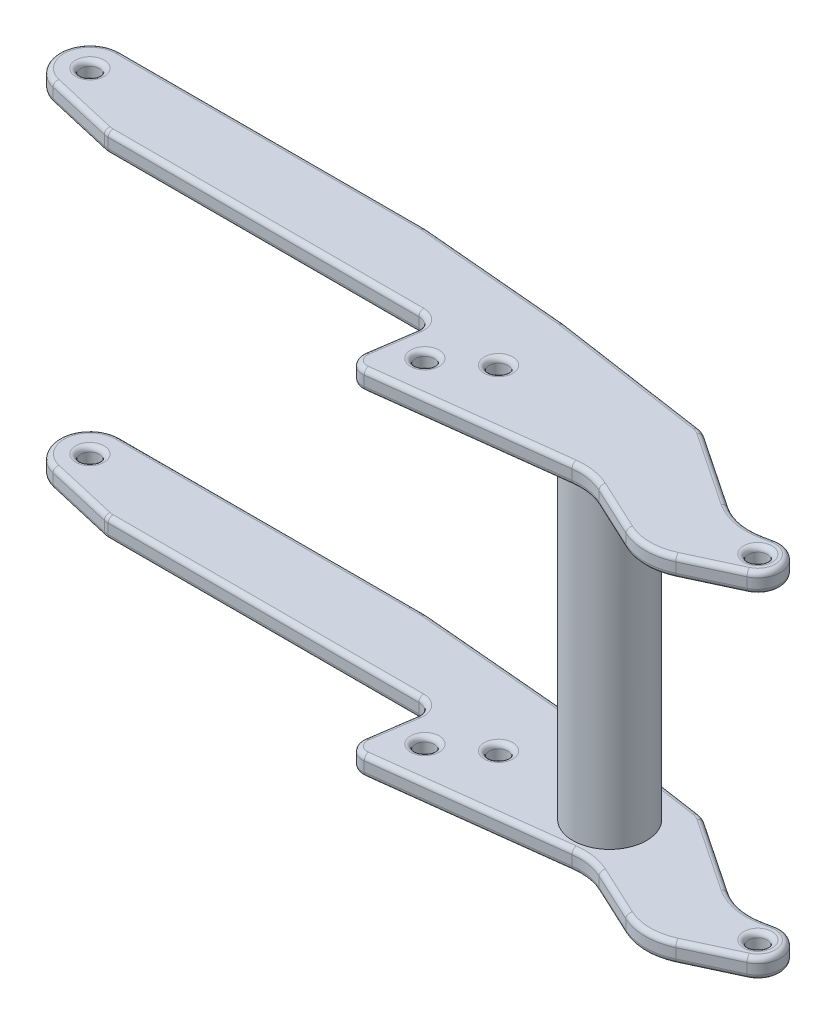
SolidWorks part; units mm, degrees
ref_plane "Front Plane" through (0, 0, 0) normal (0, 0, 1) x (1, 0, 0)
ref_plane "Top Plane" through (0, 0, 0) normal (0, 1, 0) x (1, 0, 0)
ref_plane "Right Plane" through (0, 0, 0) normal (1, 0, 0) x (0, 0, -1)
sketch "Sketch1" plane through (0, 0, 0) normal (0, 1, 0) x (1, 0, 0)
  line L0 (2.2619, 2.5389) -> (11.3096, 2.5389) construction
  line L1 (0, 3.125) -> (31.1, 3.125)
  line L2 (31.1, 3.125) -> (46.5, 1.7777)
  line L3 (46.5, 1.7777) -> (63, -0.6441)
  line L4 (63, -0.6441) -> (70.831, -5.8964)
  line L5 (75.3488, -6.7971) -> (76.2867, -6.6097)
  line L6 (76.806, -8.8246) -> (76.806, -2.115) construction
  line L7 (77.7673, -10.8865) -> (72.8208, -13.1928)
  line L8 (67.7494, -13.1926) -> (62.6097, -10.7957)
  line L9 (59.3428, -10.2781) -> (40.5062, -12.5902)
  line L10 (38.8949, -10.9405) -> (39.5728, -6.3216)
  line L11 (38.1382, -4.661) -> (6.297, -4.661)
  line L12 (6.297, -4.661) -> (-0.703, -3.0449)
  circle A0 centre (0, 0) radius 0.95
  arc A1 (0, 3.125) -> (-0.703, -3.0449) centre (0, 0) ccw
  arc A2 (70.831, -5.8964) -> (75.3488, -6.7971) centre (74.1731, -0.9134) ccw
  circle A3 centre (76.806, -8.8246) radius 0.95
  arc A4 (76.2867, -6.6097) -> (77.7673, -10.8865) centre (76.806, -8.8246) cw
  arc A5 (72.8208, -13.1928) -> (67.7494, -13.1926) centre (70.2853, -7.7549) cw
  arc A6 (62.6097, -10.7957) -> (59.3428, -10.2781) centre (60.0738, -16.2334) ccw
  arc A7 (40.5062, -12.5902) -> (38.8949, -10.9405) centre (40.3295, -11.151) cw
  arc A8 (39.5728, -6.3216) -> (38.1382, -4.661) centre (38.1382, -6.111) ccw
  circle A9 centre (42.6057, -8.5156) radius 0.95
  circle A10 centre (46.9557, -5.3656) radius 0.95
  point P18 (73, -6.7976)
  point P29 (38.6187, -12.8219)
  dimension "D1" = 1.9
  dimension "D2" = 3.125
  dimension "D9" = 6
  dimension "D10" = 0.5193
  dimension "D15" = 1.9
  dimension "D16" = 6
  dimension "D20" = 6
  dimension "D24" = 1.45
  dimension "D25" = 1.45
  dimension "D28" = 1.9
  dimension "D29" = 1.9
  dimension "D3" = 31.1
  dimension "D4" = 175
  dimension "D5" = 46.5
  dimension "D6" = 176.65
  dimension "D7" = 63
  dimension "D8" = 154.5
  dimension "D11" = 1.4572
  dimension "D12" = 10
  dimension "D13" = 5.2523
  dimension "D14" = 2.2149
  dimension "D17" = 130
  dimension "D18" = 4.9465
  dimension "D19" = 7.2964
  dimension "D21" = 148
  dimension "D22" = 20.7241
  dimension "D23" = 15.9469
  dimension "D26" = 167
  dimension "D27" = 7
  dimension "D30" = 2.2762
  dimension "D31" = 2.6354
  dimension "D32" = 4.35
  dimension "D33" = 3.15
extrude "Boss-Extrude1" add sketch "Sketch1" along normal mid plane 36
fillet "Fillet1" radius 2 4 edges at (6.297, 0, 4.661) (63, 0, 0.6441) (46.5, 0, -1.7777) (31.1, 0, -3.125)
sketch "Sketch2" plane through (0, 0, 0) normal (0, 0, 1) x (1, 0, 0)
  line L0 (67.7494, -18) -> (72.8208, -18) construction
  line L1 (-27.7185, 16) -> (106.6106, 16)
  line L2 (-27.7185, 16) -> (-27.7185, -16)
  line L3 (-27.7185, -16) -> (106.6106, -16)
  line L4 (106.6106, 16) -> (106.6106, -16)
  point P6 (70.2851, -18)
  dimension "D1" = 2
  dimension "D2" = 2
extrude "Cut-Extrude1" cut sketch "Sketch2" against normal mid plane 36
sketch "Sketch4" plane through (0, 0, 0) normal (0, 1, 0) x (1, 0, 0)
  circle A0 centre (58.65, -5.75) radius 3.75
  dimension "D1" = 58.65
  dimension "D3" = 7.5
  dimension "D2" = 5.75
extrude "Boss-Extrude2" add sketch "Sketch4" along normal mid plane 36
fillet "Fillet2" radius 0.5 104 edges at (46.9557, 18, 6.3156) (76.806, 18, 9.7746) (-3.1049, 18, -0.3538) (15.5063, 18, -3.125) (31.0999, 18, -3.1231) (38.8144, 18, -2.4501) (46.4999, 18, -1.7768) (54.5551, 18, -0.5954) (62.9818, 18, 0.6913) (67.1034, 18, 3.3963) (73, 18, 6.7976) (75.8177, 18, 6.7034) (78.9557, 18, 8.0803) (75.2941, 18, 12.0396) (70.2851, 18, 13.7549) (65.1796, 18, 11.9942) (61.0127, 18, 10.3074) (49.9245, 18, 11.4342) (39.2922, 18, 12.1642) (39.2339, 18, 8.631) (39.2354, 18, 5.163) (22.3316, 18, 4.661) (6.2985, 18, 4.6481) (2.686, 18, 3.8273) (0, 18, 0.95) (42.6057, 18, 9.4656) (15.5063, -16, -3.125) (38.8144, -16, -2.4501) (-3.1049, -16, -0.3538) (46.4999, -16, -1.7768) (54.5551, -16, -0.5954) (2.686, -16, 3.8273) (62.9818, -16, 0.6913) (6.2985, -16, 4.6481) (67.1034, -16, 3.3963) (73, -16, 6.7976) (75.8177, -16, 6.7034) (78.9557, -16, 8.0803) (75.2941, -16, 12.0396) (70.2851, -16, 13.7549) (65.1796, -16, 11.9942) (61.0127, -16, 10.3074) (49.9245, -16, 11.4342) (39.2922, -16, 12.1642) (39.2339, -16, 8.631) (39.2354, -16, 5.163) (22.3316, -16, 4.661) (46.9557, -16, 4.4156) (42.6057, -16, 7.5656) (76.806, -16, 7.8746) (0, -16, -0.95) (46.9557, -18, 6.3156) (42.6057, -18, 9.4656) (76.806, -18, 9.7746) (0, -18, 0.95) (-3.1049, -18, -0.3538) (2.686, -18, 3.8273) (22.3316, -18, 4.661) (39.2354, -18, 5.163) (39.2339, -18, 8.631) (39.2922, -18, 12.1642) (49.9245, -18, 11.4342) (61.0127, -18, 10.3074) (65.1796, -18, 11.9942) (70.2851, -18, 13.7549) (75.2941, -18, 12.0396) (78.9557, -18, 8.0803) (75.8177, -18, 6.7034) (73, -18, 6.7976) (67.1034, -18, 3.3963) (54.5551, -18, -0.5954) (38.8144, -18, -2.4501) (31.0999, -18, -3.1231) (46.4999, -18, -1.7768) (62.9818, -18, 0.6913) (6.2985, -18, 4.6481) (31.0999, -16, -3.1231) (-3.1049, 16, -0.3538) (2.686, 16, 3.8273) (22.3316, 16, 4.661) (39.2354, 16, 5.163) (39.2339, 16, 8.631) (39.2922, 16, 12.1642) (49.9245, 16, 11.4342) (61.0127, 16, 10.3074) (65.1796, 16, 11.9942) (70.2851, 16, 13.7549) (75.2941, 16, 12.0396) (78.9557, 16, 8.0803) (75.8177, 16, 6.7034) (73, 16, 6.7976) (67.1034, 16, 3.3963) (54.5551, 16, -0.5954) (38.8144, 16, -2.4501) (15.5063, 16, -3.125) (0, 16, 0.95) (76.806, 16, 9.7746) (42.6057, 16, 9.4656) (46.9557, 16, 6.3156) (6.2985, 16, 4.6481) (31.0999, 16, -3.1231) (46.4999, 16, -1.7768) (62.9818, 16, 0.6913) (15.5063, -18, -3.125)
